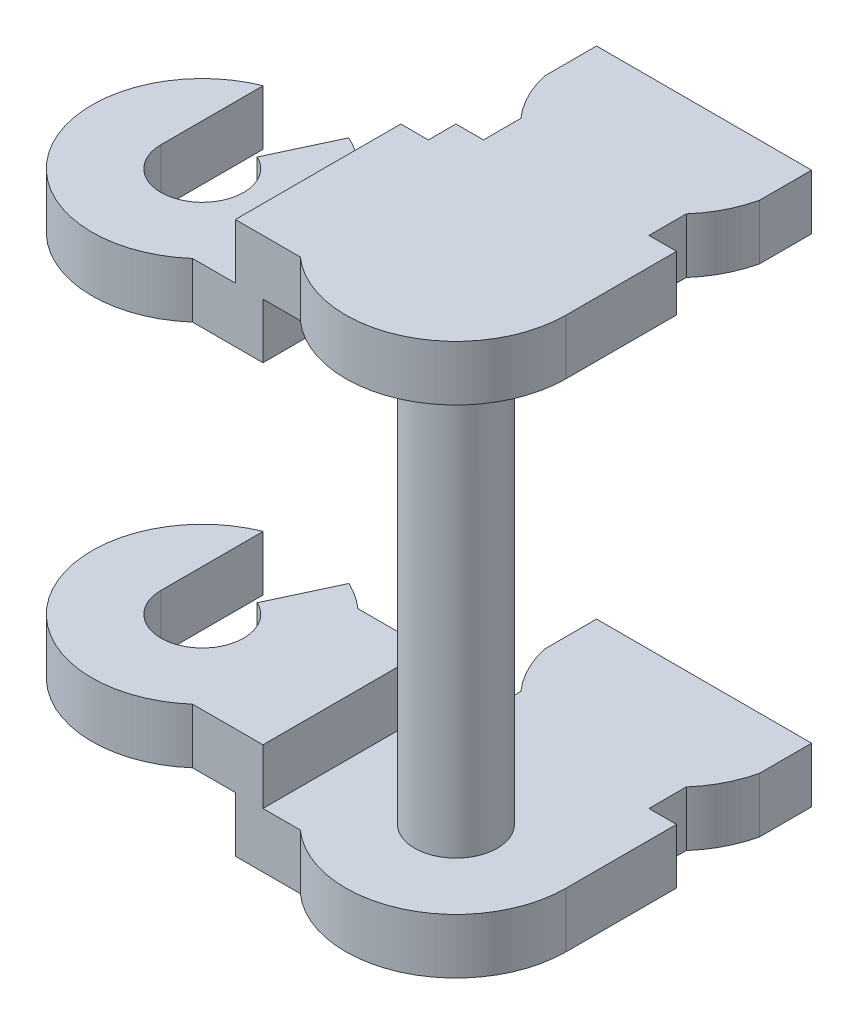
SolidWorks part; units mm, degrees
ref_plane "前视基准面" through (0, 0, 0) normal (0, 0, 1) x (1, 0, 0)
ref_plane "上视基准面" through (0, 0, 0) normal (0, 1, 0) x (1, 0, 0)
ref_plane "右视基准面" through (0, 0, 0) normal (1, 0, 0) x (0, 0, -1)
sketch "草图1" plane through (0, 0, 0) normal (0, 1, 0) x (1, 0, 0)
  circle A0 centre (0, 0) radius 0.75
extrude "凸台-拉伸1" add sketch "草图1" along normal blind 4 and the other way blind 4
sketch "草图2" plane through (0, 4, 0) normal (0, 1, 0) x (-1, 0, 0)
  circle A0 centre (0, 0) radius 2
extrude "凸台-拉伸2" add sketch "草图2" along normal blind 1
sketch "草图3" plane through (0, -4, 0) normal (0, -1, 0) x (1, 0, 0)
  circle A0 centre (0, 0) radius 2
extrude "凸台-拉伸3" add sketch "草图3" along normal blind 1
sketch "草图6" plane through (0, 5, 0) normal (0, 1, 0) x (-1, 0, 0)
  line L1 (1, -1.5) -> (2.5, -1.5)
  line L2 (1, -1.5) -> (1, 1.5)
  line L3 (1, 1.5) -> (2.5, 1.5)
  line L4 (2.5, -1.5) -> (2.5, 1.5)
extrude "凸台-拉伸6" add sketch "草图6" against normal up to surface (1 mm away) up to face at (0, 4, 0.75)
sketch "草图7" plane through (0, -5, 0) normal (0, -1, 0) x (1, 0, 0)
  line L1 (-1, -1.5) -> (-2.5, -1.5)
  line L2 (-1, -1.5) -> (-1, 1.5)
  line L3 (-1, 1.5) -> (-2.5, 1.5)
  line L4 (-2.5, -1.5) -> (-2.5, 1.5)
extrude "凸台-拉伸8" add sketch "草图7" against normal up to surface (1 mm away) up to face at (0, -4, -0.75)
sketch "草图8" plane through (-2.5, 0, 0) normal (-1, 0, 0) x (0, 0, 1)
  line L1 (-1.5, 5) -> (1.5, 5)
  line L2 (-1.5, 5) -> (-1.5, 3)
  line L3 (-1.5, 3) -> (1.5, 3)
  line L4 (1.5, 5) -> (1.5, 3)
  line L5 (-1.5, -5) -> (1.5, -5)
  line L6 (-1.5, -5) -> (-1.5, -3)
  line L7 (-1.5, -3) -> (1.5, -3)
  line L8 (1.5, -5) -> (1.5, -3)
extrude "凸台-拉伸9" add sketch "草图8" against normal blind 0.5
sketch "草图9" plane through (0, 3, 0) normal (0, -1, 0) x (1, 0, 0)
  line L1 (-2.5, -1.5) -> (-3.2771, -1.5)
  line L2 (-2.5, -1.5) -> (-2.5, 1.5)
  line L3 (-2.5, 1.5) -> (-3.2771, 1.5)
  arc A0 (-3.2771, 1.5) -> (-3.2771, -1.5) centre (-4.6, 0) ccw
extrude "凸台-拉伸10" add sketch "草图9" against normal blind 1
extrude "凸台-拉伸11" add sketch "草图9<2>" along normal blind 1 from offset 6
sketch "草图9<2>" plane through (0, 3, 0) normal (0, -1, 0) x (1, 0, 0) same geometry as "草图9"
sketch "草图10" plane through (0, 4, 0) normal (0, 1, 0) x (-1, 0, 0)
  line L0 (5.35, 0) -> (5.35, -1.854)
  line L1 (4.283, -0.6797) -> (3.7548, -1.8126)
  arc A0 (5.35, 0) -> (4.283, -0.6797) centre (4.6, 0) ccw
  arc A1 (3.7548, -1.8126) -> (5.35, -1.854) centre (4.6, 0) ccw
extrude "切除-拉伸1" cut sketch "草图10" against normal through all
sketch "草图11" plane through (0, 5, 0) normal (0, 1, 0) x (1, 0, 0)
  line L0 (-2, 0) -> (2, 0)
  line L1 (2, 0) -> (2, 2)
  line L2 (0, 0) -> (0, 2) construction
  line L3 (0, 2) -> (0, 4) construction
  line L4 (0, 4) -> (0, 4.5) construction
  line L5 (0, 2) -> (1.5, 2) construction
  line L6 (1.5, 2) -> (1.5, 2.6771)
  line L7 (-1.95, 4.5) -> (1.95, 4.5)
  line L8 (1.95, 4.5) -> (1.95, 3.5556)
  line L9 (1.5, 2) -> (2, 2)
  line L10 (-2, 0) -> (-2, 2)
  line L11 (-1.5, 2) -> (-2, 2)
  line L12 (-1.5, 2) -> (-1.5, 2.6771)
  line L13 (-1.95, 4.5) -> (-1.95, 3.5556)
  arc A0 (-1.3229, -1.5) -> (-1.3229, 1.5) centre (0, 0) ccw construction
  arc A1 (1.5, 2.6771) -> (1.95, 3.5556) centre (0, 4) ccw
  arc A2 (-1.5, 2.6771) -> (-1.95, 3.5556) centre (0, 4) cw
  dimension "D1" = 2
  dimension "D7" = 2
  dimension "D2" = 2
  dimension "D3" = 0.5
  dimension "D4" = 90
  dimension "D5" = 1.5
  dimension "D6" = 1.95
extrude "凸台-拉伸12" add sketch "草图11" against normal blind 1
mirror "镜向1" about plane through (0, 0, 0) normal (0, 1, 0) of "凸台-拉伸12"
